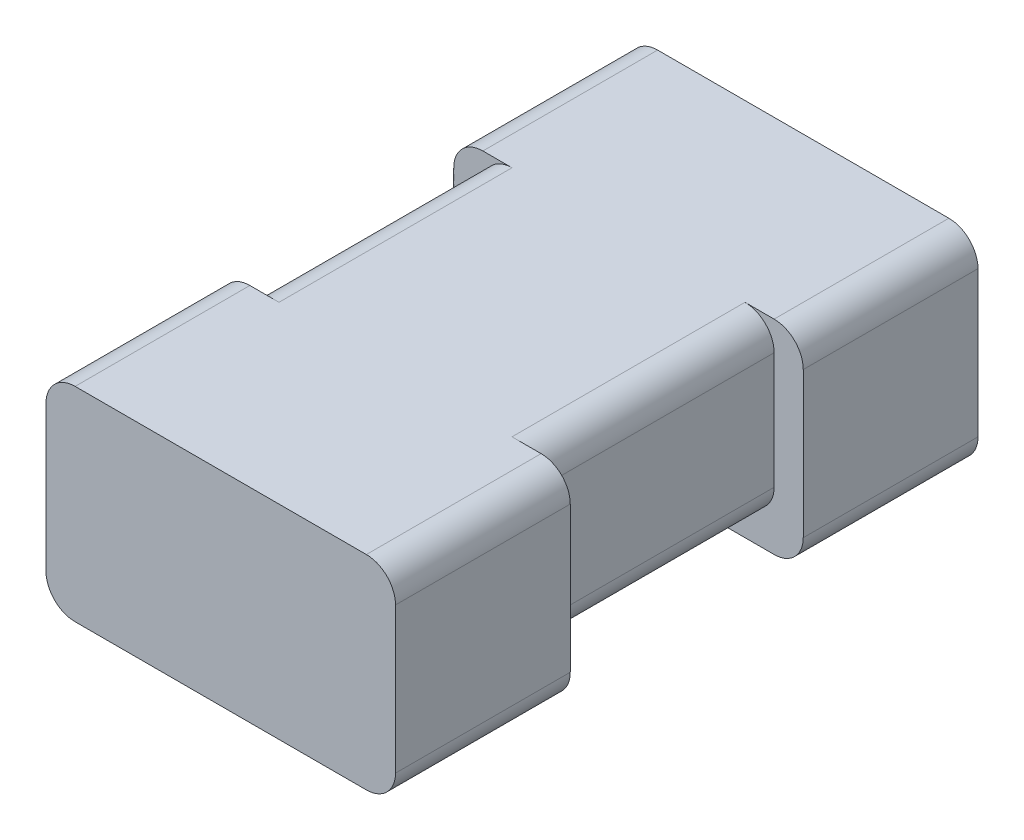
SolidWorks part; units mm, degrees
ref_plane "Front Plane" through (0, 0, 0) normal (0, 0, 1) x (1, 0, 0)
ref_plane "Top Plane" through (0, 0, 0) normal (0, 1, 0) x (1, 0, 0)
ref_plane "Right Plane" through (0, 0, 0) normal (1, 0, 0) x (0, 0, -1)
sketch "Sketch2" plane through (0, 0, 0) normal (0, 0, 1) x (1, 0, 0)
  line L1 (0, 0) -> (0.5, 0)
  line L2 (0, 0) -> (0, -0.3)
  line L3 (0, -0.3) -> (0.5, -0.3)
  line L4 (0.5, 0) -> (0.5, -0.3)
  dimension "D1" = 0.5
  dimension "D2" = 0.3
extrude "Boss-Extrude1" add sketch "Sketch2" along normal blind 0.4
sketch "Sketch3" plane through (0, 0, 0.4) normal (0, 0, 1) x (1, 0, 0)
  line L0 (0, -0.3) -> (0.5, -0.3) construction
  line L1 (-0.05, 0) -> (0.55, 0)
  line L2 (-0.05, 0) -> (-0.05, -0.35)
  line L3 (-0.05, -0.35) -> (0.55, -0.35)
  line L4 (0.55, 0) -> (0.55, -0.35)
  line L5 (0.5, 0) -> (0, 0) construction
  point P6 (0.25, -0.3)
  point P7 (0.25, -0.35)
  dimension "D1" = 0.6
  dimension "D2" = 0.35
extrude "Boss-Extrude2" add sketch "Sketch3" along normal blind 0.3
sketch "Sketch4" plane through (0, 0, 0) normal (0, 0, -1) x (-1, 0, 0)
  line L0 (0.05, 0) -> (0.05, -0.35) construction
  line L1 (-0.55, 0) -> (0.05, 0)
  line L2 (-0.55, 0) -> (-0.55, -0.35)
  line L3 (-0.55, -0.35) -> (0.05, -0.35)
  line L4 (0.05, 0) -> (0.05, -0.35)
  line L5 (-0.55, -0.35) -> (-0.55, 0) construction
  line L6 (0.05, -0.35) -> (-0.55, -0.35) construction
  line L7 (-0.5, 0) -> (0, 0) construction
extrude "Boss-Extrude4" add sketch "Sketch4" along normal blind 0.3
fillet "Fillet2" radius 0.05 12 edges at (0.55, -0.35, 0.55) (-0.05, -0.35, 0.55) (-0.05, -0.35, -0.15) (0.55, -0.35, -0.15) (0.5, -0.3, 0.2) (0, -0.3, 0.2) (0.55, 0, 0.55) (-0.05, 0, 0.55) (0, 0, 0.2) (0.5, 0, 0.2) (0.55, 0, -0.15) (-0.05, 0, -0.15)
